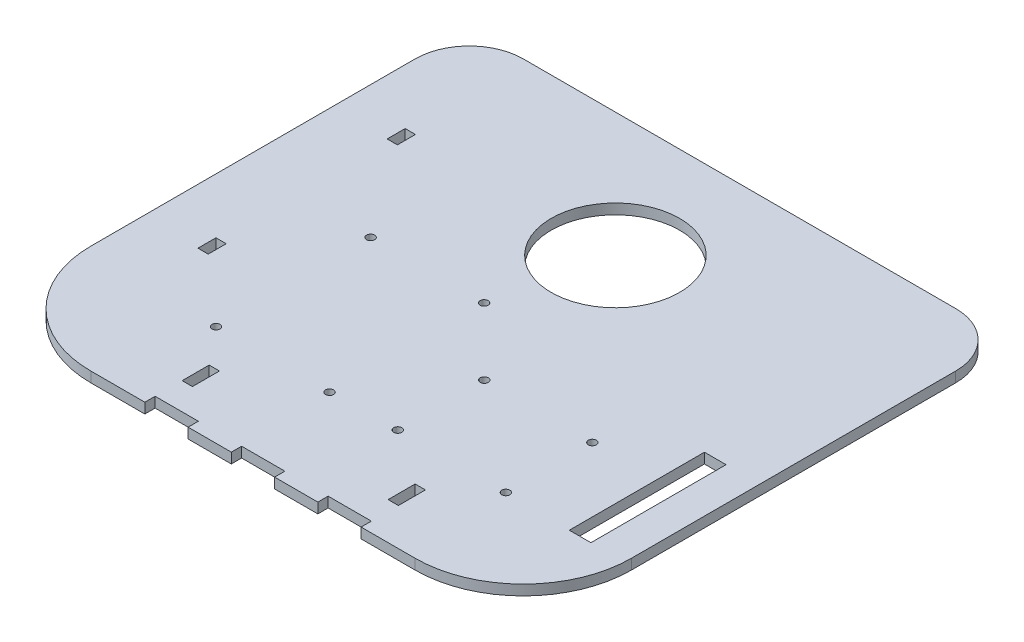
SolidWorks part; units mm, degrees
ref_plane "Front Plane" through (0, 0, 0) normal (0, 0, 1) x (1, 0, 0)
ref_plane "Top Plane" through (0, 0, 0) normal (0, 1, 0) x (1, 0, 0)
ref_plane "Right Plane" through (0, 0, 0) normal (1, 0, 0) x (0, 0, -1)
sketch "Sketch1" plane through (0, 0, 0) normal (0, 1, 0) x (1, 0, 0)
  line L1 (-127, 114.3) -> (127, 114.3)
  line L2 (-127, 114.3) -> (-127, -114.3)
  line L3 (-127, -114.3) -> (127, -114.3)
  line L4 (127, 114.3) -> (127, -114.3)
  line L5 (-127, 114.3) -> (127, -114.3) construction
  line L6 (-127, -114.3) -> (127, 114.3) construction
  point P0 (0, 0)
  dimension "D1" = 254
  dimension "D2" = 228.6
extrude "Boss-Extrude1" add sketch "Sketch1" along normal blind 4.826
sketch "Sketch4" plane through (0, 4.826, 0) normal (0, 1, 0) x (1, 0, 0)
  line L0 (0, -114.3) -> (0, 114.3) construction
  line L1 (-127, -114.3) -> (127, -114.3) construction
  line L2 (127, 114.3) -> (-127, 114.3) construction
  line L3 (-127, 88.9) -> (-101.6, 88.9) construction
  line L4 (-127, 114.3) -> (-127, -114.3) construction
  line L5 (-101.6, 88.9) -> (-101.6, 114.3) construction
  line L6 (-127, 88.9) -> (-127, 114.3)
  line L7 (-127, 114.3) -> (-101.6, 114.3)
  line L8 (127, 88.9) -> (127, 114.3)
  line L9 (127, 114.3) -> (101.6, 114.3)
  arc A0 (-127, 88.9) -> (-101.6, 114.3) centre (-101.6, 88.9) cw
  arc A1 (127, 88.9) -> (101.6, 114.3) centre (101.6, 88.9) ccw
  dimension "D1" = 25.4
  dimension "D2" = 25.4
extrude "Cut-Extrude3" cut sketch "Sketch4" against normal blind 4.826
sketch "Sketch19" plane through (0, 4.826, 0) normal (0, 1, 0) x (1, 0, 0)
  line L0 (-101, -39.1583) -> (-101, -30.6917) construction
  line L1 (-101, -39.1583) -> (-96.174, -39.1583) construction
  line L2 (-96.174, -39.1583) -> (-96.174, -30.6917) construction
  line L3 (-101, -30.6917) -> (-96.174, -30.6917) construction
  line L4 (-101, 49.7417) -> (-101, 58.2083) construction
  line L5 (-101, 49.7417) -> (-96.174, 49.7417) construction
  line L6 (-96.174, 49.7417) -> (-96.174, 58.2083) construction
  line L7 (-101, 58.2083) -> (-96.174, 58.2083) construction
  line L8 (-101, -39.1583) -> (-101, -30.6917)
  line L9 (-101, -39.1583) -> (-96.174, -39.1583)
  line L10 (-96.174, -39.1583) -> (-96.174, -30.6917)
  line L11 (-101, -30.6917) -> (-96.174, -30.6917)
  line L12 (-101, 49.7417) -> (-101, 58.2083)
  line L13 (-101, 49.7417) -> (-96.174, 49.7417)
  line L14 (-96.174, 49.7417) -> (-96.174, 58.2083)
  line L15 (-101, 58.2083) -> (-96.174, 58.2083)
extrude "Cut-Extrude16" cut sketch "Sketch19" against normal through all
fillet "Fillet11" radius 50.8 2 edges at (-127, 2.413, 114.3) (127, 2.413, 114.3)
sketch "Sketch20" plane through (0, 0, 0) normal (0, -1, 0) x (1, 0, 0)
  line L1 (101, 66.675) -> (111.16, 66.675)
  line L2 (101, 66.675) -> (101, 3.175)
  line L3 (101, 3.175) -> (111.16, 3.175)
  line L4 (111.16, 66.675) -> (111.16, 3.175)
  dimension "D1" = 10.16
extrude "Cut-Extrude17" cut sketch "Sketch20" against normal through all
sketch "Sketch23" plane through (0, 4.826, 0) normal (0, 1, 0) x (1, 0, 0)
  circle A0 centre (70.7411, -25.5764) radius 1.905 construction
  circle A1 centre (70.7411, -66.2164) radius 1.905 construction
  circle A2 centre (19.9411, -25.5764) radius 1.905 construction
  circle A3 centre (19.9411, -66.2164) radius 1.905 construction
  circle A4 centre (-11.4804, 5.7926) radius 1.905 construction
  circle A5 centre (-64.8204, 5.7926) radius 1.905 construction
  circle A6 centre (-64.8204, -66.8514) radius 1.905 construction
  circle A7 centre (-11.4804, -66.8514) radius 1.905 construction
  circle A8 centre (70.7411, -25.5764) radius 1.905
  circle A9 centre (70.7411, -66.2164) radius 1.905
  circle A10 centre (19.9411, -25.5764) radius 1.905
  circle A11 centre (19.9411, -66.2164) radius 1.905
  circle A12 centre (-11.4804, 5.7926) radius 1.905
  circle A13 centre (-64.8204, 5.7926) radius 1.905
  circle A14 centre (-64.8204, -66.8514) radius 1.905
  circle A15 centre (-11.4804, -66.8514) radius 1.905
extrude "Cut-Extrude18" cut sketch "Sketch23" against normal through all
sketch "Sketch24" plane through (0, 0, 0) normal (0, -1, 0) x (1, 0, 0)
  line L0 (50.8, 114.3) -> (50.8, 109.474) construction
  line L1 (50.8, 114.3) -> (50.8, 109.474)
  line L2 (50.8, 114.3) -> (50.8, 109.474)
  line L3 (30.48, 114.3) -> (50.8, 114.3) construction
  line L4 (30.48, 109.474) -> (50.8, 109.474) construction
  line L5 (30.48, 114.3) -> (30.48, 109.474) construction
  line L6 (10.16, 114.3) -> (10.16, 109.474) construction
  line L7 (-10.16, 109.474) -> (10.16, 109.474) construction
  line L8 (-10.16, 114.3) -> (-10.16, 109.474) construction
  line L9 (-10.16, 114.3) -> (10.16, 114.3) construction
  line L10 (-30.48, 114.3) -> (-30.48, 109.474) construction
  line L11 (-50.8, 114.3) -> (-30.48, 114.3) construction
  line L12 (-50.8, 114.3) -> (-50.8, 109.474) construction
  line L13 (-50.8, 109.474) -> (-30.48, 109.474) construction
  line L14 (30.48, 114.3) -> (50.8, 114.3)
  line L15 (50.8, 114.3) -> (50.8, 109.474)
  line L16 (30.48, 109.474) -> (50.8, 109.474)
  line L17 (30.48, 114.3) -> (30.48, 109.474)
  line L18 (10.16, 114.3) -> (10.16, 109.474)
  line L19 (-10.16, 109.474) -> (10.16, 109.474)
  line L20 (-10.16, 114.3) -> (-10.16, 109.474)
  line L21 (-10.16, 114.3) -> (10.16, 114.3)
  line L22 (-30.48, 114.3) -> (-30.48, 109.474)
  line L23 (-50.8, 114.3) -> (-30.48, 114.3)
  line L24 (-50.8, 114.3) -> (-50.8, 109.474)
  line L25 (-50.8, 109.474) -> (-30.48, 109.474)
  line M21 (76.2, 114.3) -> (-76.2, 114.3)
extrude "Cut-Extrude19" cut sketch "Sketch24" against normal through all contours L17 L16 L1 M21 | L24 L25 L22 M21 | L21 L18 L19 L20 region at (-40.64, 0, 111.887) region at (40.64, 0, 111.887)
sketch "Sketch26" plane through (0, 0, 0) normal (0, -1, 0) x (1, 0, 0)
  circle A0 centre (0, -55.982) radius 30.1625 construction
  circle A1 centre (0, -55.982) radius 30.1625
extrude "Cut-Extrude20" cut sketch "Sketch26" against normal through all
sketch "Sketch27" plane through (0, 0, 0) normal (0, -1, 0) x (1, 0, 0)
  line L0 (-45.974, 84.074) -> (-45.974, 96.774) construction
  line L1 (-50.8, 96.774) -> (-45.974, 96.774) construction
  line L2 (-50.8, 84.074) -> (-50.8, 96.774) construction
  line L3 (-50.8, 84.074) -> (-45.974, 84.074) construction
  line L4 (50.8, 84.074) -> (50.8, 96.774) construction
  line L5 (50.8, 84.074) -> (45.974, 84.074) construction
  line L6 (45.974, 84.074) -> (45.974, 96.774) construction
  line L7 (50.8, 96.774) -> (45.974, 96.774) construction
  line L8 (-45.974, 84.074) -> (-45.974, 96.774)
  line L9 (-50.8, 96.774) -> (-45.974, 96.774)
  line L10 (-50.8, 84.074) -> (-50.8, 96.774)
  line L11 (-50.8, 84.074) -> (-45.974, 84.074)
  line L12 (50.8, 84.074) -> (50.8, 96.774)
  line L13 (50.8, 84.074) -> (45.974, 84.074)
  line L14 (45.974, 84.074) -> (45.974, 96.774)
  line L15 (50.8, 96.774) -> (45.974, 96.774)
extrude "Cut-Extrude21" cut sketch "Sketch27" against normal through all
equation "\"MDF\"= 0.19in"
equation "\"GenDiameter\"= 60mm"
equation "\"GenCutDiameter\" = 1.8in"
equation "\"GenCutDistance\" = 1"
equation "\"TowerHeight\" = 6in"
equation "\"TowerFrontBase\" = 3in"
equation "\"FunnelHeight\" = 1in"
equation "\"FunnelAngle\" = 20"
equation "\"TowerSideBase\" = 3in"
equation "\"BaseLength\" = 9in"
equation "\"BaseWidth\" = 10in"
equation "\"WheelHoleLength\" = 3.25in"
equation "\"WheelHoleWidth\" = 26mm"
equation "\"DropLength\" = 1in"
equation "\"D1@Sketch1\"=\"BaseWidth\""
equation "\"D2@Sketch1\"=\"BaseLength\""
equation "\"D1@Boss-Extrude1\"=\"MDF\""
equation "\"WheelHoleFromBack\" = 1.5in"
equation "\"DropWidth\" = 8.5in"
equation "\"BumperWidth\" = 2in"
equation "\"D1@Cut-Extrude3\"=\"MDF\""
equation "\"DropWidthTop\" = 0in"
